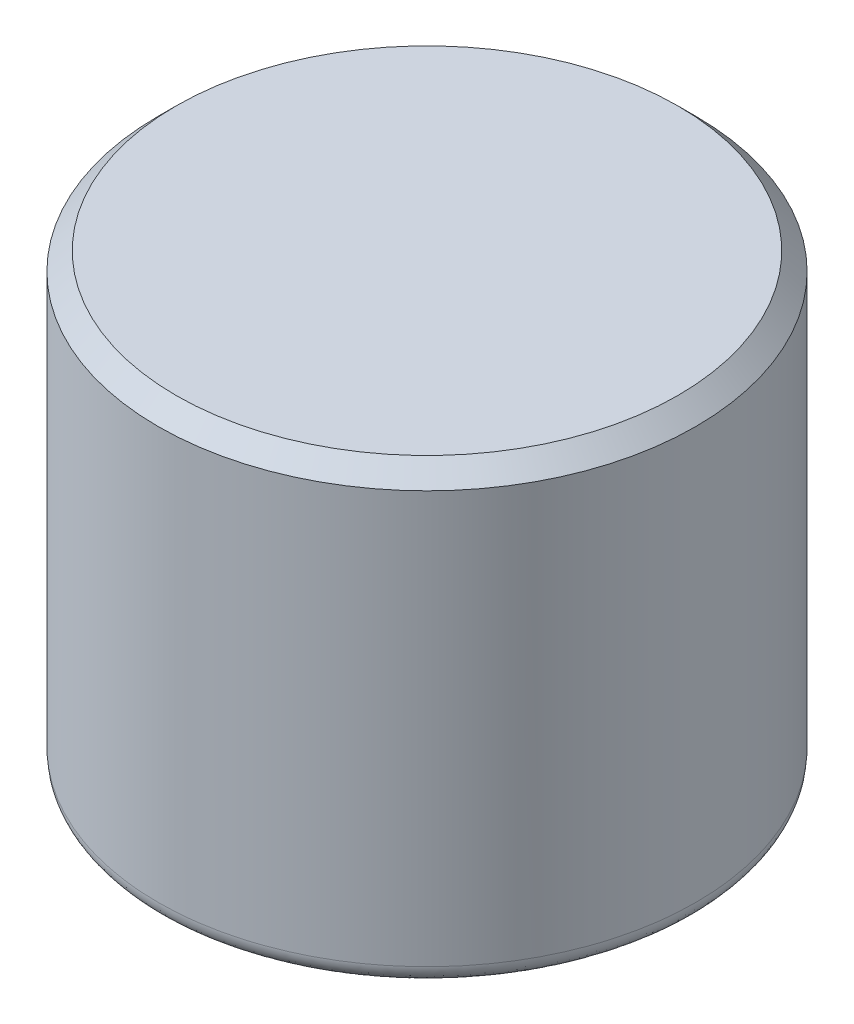
SolidWorks part; units mm, degrees
ref_plane "Front Plane" through (0, 0, 0) normal (0, 0, 1) x (1, 0, 0)
ref_plane "Top Plane" through (0, 0, 0) normal (0, 1, 0) x (1, 0, 0)
ref_plane "Right Plane" through (0, 0, 0) normal (1, 0, 0) x (0, 0, -1)
sketch "Sketch2" plane through (0, 0, 0) normal (0, 0, 1) x (1, 0, 0)
  line L0 (0, 0) -> (15, 0)
  line L1 (15, 0) -> (15, -25)
  line L2 (15, -25) -> (6.7641, -25)
  line L3 (6.7641, -25) -> (3.3, -23)
  line L4 (3.3, -23) -> (3.3, -13)
  line L5 (3.3, -13) -> (0, -13)
  line L6 (0, -13) -> (0, 0)
  point P4 (295.0812, -702.8727)
  point P9 (34.848, -355.8952)
  point P10 (197.4937, -401.9781)
  point P11 (20.7255, -247.8912)
  point P12 (49.972, -339.1757)
  point P13 (100.4887, -336.5169)
  point P14 (6.6612, -326.7455)
  point P15 (3.6206, -311.543)
  point P16 (7.859, -30)
  point P17 (4.201, -25.1615)
  point P18 (4.9326, -30)
  dimension "D1" = 15
  dimension "D2" = 12
  dimension "D3" = 25
  dimension "D4" = 10
  dimension "D5" = 150
  dimension "D6" = 3.3
ref_axis "Axis1" through (0, -28.875, 0) along (0, 1, 0)
revolve "Revolve1" add sketch "Sketch2" angle 360 about axis through (0, -28.875, 0) along (0, 1, 0)
chamfer "Chamfer1" distance 1 angle 45 1 edges at (0, 0, -15)
fillet "Fillet1" radius 1 3 edges at (0, -23, -3.3) (0, -25, -6.7641) (0, -25, -15) conic rho 0.45
sketch "Sketch3" plane through (0, 0, 0) normal (1, 0, 0) x (0, 0, -1)
  line L0 (0, -28.875) -> (0, 1.375) construction
  line L1 (-14, -25) -> (14, -25) construction
  circle A0 centre (0, -16) radius 1.1303
  point P4 (0, 0)
  point P7 (0, 0)
  dimension "D1" = 2.2606
  dimension "D2" = 9
extrude "Cut-Extrude1" cut sketch "Sketch3" against normal blind 15
ref_plane "Plane3" through (-15, 0, 0) normal (1, 0, 0) x (0, 0, -1)
thread "Thread1" pitch 0.635 method cut profile "Thread Profile3" start angle 0, offset 1, length 14, pitch 0.635, diameter 2.2606
ref_plane "Plane4" through (-16, -16, -1.1303) normal (0, -1, 0) x (0, 0, -1)
sketch "Thread Profile3" plane through (-16, -16, -1.1303) normal (0, -1, 0) x (0, 0, -1)
  line L0 (0, 0) -> (0, 0.635) construction
  line L1 (0, 0) -> (0.3437, 0.1984)
  line L2 (0.3437, 0.1984) -> (0.3437, 0.2778)
  line L3 (0.3437, 0.2778) -> (0, 0.4762)
  line L4 (0.3437, 0.2381) -> (0, 0.2381) construction
  line L11 (0, 0) -> (0, 0.4762)
  point P2 (0, 0)
  dimension "Pitch" = 0.635
  dimension "Profile_Angle" = 60
  dimension "Profile_Land" = 0.0794
  dimension "Profile_Height" = 0.3437
sketch "Sketch12" plane through (0, 0, 0) normal (0, 0, 1) x (1, 0, 0)
  line L0 (0, -28.875) -> (0, 1.375) construction
  line L1 (-14, -25) -> (14, -25) construction
  circle A0 centre (0, -16) radius 1.1303
  point P2 (0, -19.123)
  dimension "D2" = 2.2606
  dimension "D1" = 9
extrude "Cut-Extrude2" [suppressed] cut sketch "Sketch12" along normal blind 15
ref_plane "Plane5" through (0, 0, 15) normal (0, 0, 1) x (1, 0, 0)
thread "Thread2" [suppressed] pitch 0.635 start angle 0, offset 1, length 14, pitch 0.635, diameter 2.2606
ref_plane "Plane6" through (-1.1303, -16, 16) normal (0, -1, 0) x (-1, 0, 0)
sketch "Thread Profile4" plane through (-1.1303, -16, 16) normal (0, -1, 0) x (-1, 0, 0)
  line L0 (0, 0) -> (0, 0.635) construction
  line L1 (0, 0) -> (0.3437, 0.1984)
  line L2 (0.3437, 0.1984) -> (0.3437, 0.2778)
  line L3 (0.3437, 0.2778) -> (0, 0.4762)
  line L4 (0.3437, 0.2381) -> (0, 0.2381) construction
  line L11 (0, 0) -> (0, 0.4762)
  point P2 (0, 0)
  dimension "Pitch" = 0.635
  dimension "Profile_Angle" = 60
  dimension "Profile_Land" = 0.0794
  dimension "Profile_Height" = 0.3437
